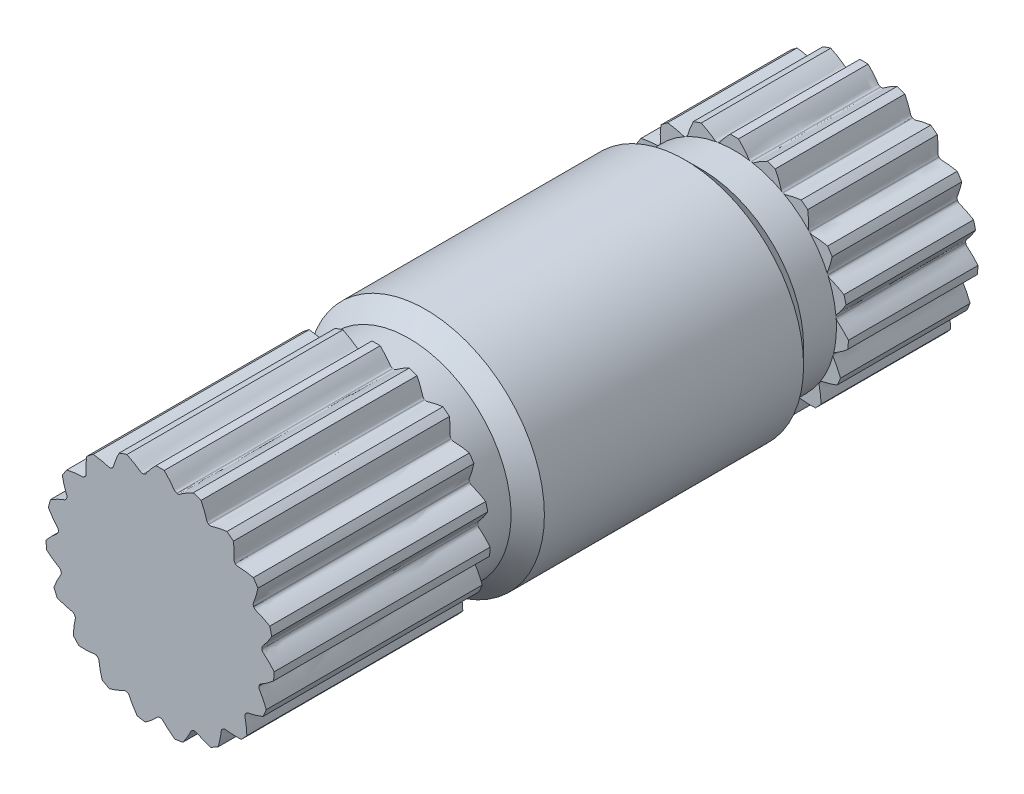
SolidWorks part; units mm, degrees
material "Alloy Steel"
ref_plane "Front Plane" through (0, 0, 0) normal (0, 0, 1) x (1, 0, 0)
ref_plane "Top Plane" through (0, 0, 0) normal (0, 1, 0) x (1, 0, 0)
ref_plane "Right Plane" through (0, 0, 0) normal (1, 0, 0) x (0, 0, -1)
sketch "Sketch12" plane through (0, 0, 0) normal (0, 0, 1) x (1, 0, 0)
  circle A0 centre (0, 0) radius 11
  dimension "D1" = 22
extrude "Boss-Extrude5" add sketch "Sketch12" along normal mid plane 30
sketch "Sketch13" plane through (0, 0, 15) normal (0, 0, 1) x (1, 0, 0)
  circle A0 centre (0, 0) radius 9.4556
  dimension "D1" = 18.9113
extrude "Boss-Extrude6" add sketch "Sketch13" along normal blind 1.587
sketch "Sketch14" plane through (0, 0, -15) normal (0, 0, -1) x (-1, 0, 0)
  circle A0 centre (0, 0) radius 9.4556
  dimension "D1" = 18.9113
extrude "Boss-Extrude7" add sketch "Sketch14" along normal blind 1.587
sketch "Sketch15" plane through (0, 0, 16.587) normal (0, 0, 1) x (1, 0, 0)
  line L0 (5.7898, -7.4758) -> (5.8078, -7.4618)
  line L1 (5.8078, -7.4618) -> (5.8257, -7.4478)
  line L2 (7.9035, -5.1908) -> (7.9159, -5.1717)
  line L3 (7.9159, -5.1717) -> (7.9284, -5.1527)
  line L4 (9.1607, -2.3432) -> (9.1663, -2.3212)
  line L5 (9.1663, -2.3212) -> (9.1719, -2.2992)
  line L6 (9.4252, 0.7582) -> (9.4233, 0.7808)
  line L7 (9.4233, 0.7808) -> (9.4214, 0.8035)
  line L8 (8.6683, 3.7775) -> (8.6592, 3.7983)
  line L9 (8.6592, 3.7983) -> (8.6501, 3.8191)
  line L10 (6.9721, 6.3874) -> (6.9567, 6.4041)
  line L11 (6.9567, 6.4041) -> (6.9413, 6.4208)
  line L12 (4.5204, 8.3051) -> (4.5004, 8.316)
  line L13 (4.5004, 8.316) -> (4.4804, 8.3268)
  line L14 (1.5788, 9.3229) -> (1.5563, 9.3267)
  line L15 (1.5563, 9.3267) -> (1.5339, 9.3304)
  line L16 (-1.5339, 9.3304) -> (-1.5563, 9.3267)
  line L17 (-1.5563, 9.3267) -> (-1.5788, 9.3229)
  line L18 (-4.4804, 8.3268) -> (-4.5004, 8.316)
  line L19 (-4.5004, 8.316) -> (-4.5204, 8.3051)
  line L20 (-6.9413, 6.4208) -> (-6.9567, 6.4041)
  line L21 (-6.9567, 6.4041) -> (-6.9721, 6.3874)
  line L22 (-8.6501, 3.8191) -> (-8.6592, 3.7983)
  line L23 (-8.6592, 3.7983) -> (-8.6683, 3.7775)
  line L24 (-9.4214, 0.8035) -> (-9.4233, 0.7808)
  line L25 (-9.4233, 0.7808) -> (-9.4252, 0.7582)
  line L26 (-9.1719, -2.2992) -> (-9.1663, -2.3212)
  line L27 (-9.1663, -2.3212) -> (-9.1607, -2.3432)
  line L28 (-7.9284, -5.1527) -> (-7.9159, -5.1717)
  line L29 (-7.9159, -5.1717) -> (-7.9035, -5.1908)
  line L30 (-5.8257, -7.4478) -> (-5.8078, -7.4618)
  line L31 (-5.8078, -7.4618) -> (-5.7898, -7.4758)
  line L32 (-3.0917, -8.9359) -> (-3.0702, -8.9433)
  line L33 (-3.0702, -8.9433) -> (-3.0487, -8.9507)
  line L34 (-0.0227, -9.4556) -> (0, -9.4556)
  line L35 (0, -9.4556) -> (0.0227, -9.4556)
  line L36 (3.0487, -8.9507) -> (3.0702, -8.9433)
  line L37 (3.0702, -8.9433) -> (3.0917, -8.9359)
  arc A0 (4.6925, -9.4774) -> (5.3676, -9.1121) centre (0, 0) ccw
  arc A1 (7.5156, -7.4402) -> (8.0355, -6.8755) centre (0, 0) ccw
  arc A2 (9.5242, -4.5968) -> (9.8326, -3.8939) centre (0, 0) ccw
  arc A3 (10.5007, -1.2552) -> (10.5641, -0.4903) centre (0, 0) ccw
  arc A4 (10.3394, 2.2224) -> (10.1509, 2.9665) centre (0, 0) ccw
  arc A5 (9.0575, 5.4591) -> (8.6377, 6.1017) centre (0, 0) ccw
  arc A6 (6.7942, 8.1043) -> (6.1885, 8.5758) centre (0, 0) ccw
  arc A7 (3.7946, 9.8713) -> (3.0686, 10.1205) centre (0, 0) ccw
  arc A8 (0.3838, 10.5685) -> (-0.3838, 10.5685) centre (0, 0) ccw
  arc A9 (-3.0686, 10.1205) -> (-3.7946, 9.8713) centre (0, 0) ccw
  arc A10 (-6.1885, 8.5758) -> (-6.7942, 8.1043) centre (0, 0) ccw
  arc A11 (-8.6377, 6.1017) -> (-9.0575, 5.4591) centre (0, 0) ccw
  arc A12 (-10.1509, 2.9665) -> (-10.3394, 2.2224) centre (0, 0) ccw
  arc A13 (-10.5641, -0.4903) -> (-10.5007, -1.2552) centre (0, 0) ccw
  arc A14 (-9.8326, -3.8939) -> (-9.5242, -4.5968) centre (0, 0) ccw
  arc A15 (-8.0355, -6.8755) -> (-7.5156, -7.4402) centre (0, 0) ccw
  arc A16 (-5.3676, -9.1121) -> (-4.6925, -9.4774) centre (0, 0) ccw
  arc A17 (-2.1181, -10.3612) -> (-1.361, -10.4876) centre (0, 0) ccw
  arc A18 (1.361, -10.4876) -> (2.1181, -10.3612) centre (0, 0) ccw
  spline S0 degree 3 poles (3.0917, -8.9359) (3.1544, -8.9142) (3.2184, -8.911) (3.3396, -8.938) (3.397, -8.9729) (3.5767, -9.0624) (3.828, -9.1783) (4.24, -9.3384) (4.5379, -9.4334) (4.6925, -9.4774) knots 0 0 0 0 0.125 0.125 0.25 0.25 0.5 0.75 1 1 1 1
  spline S1 degree 3 poles (5.3676, -9.1121) (5.4153, -8.9586) (5.4987, -8.6572) (5.5901, -8.2247) (5.6305, -7.951) (5.6538, -7.7516) (5.656, -7.6845) (5.6997, -7.5682) (5.7374, -7.5164) (5.7898, -7.4758) knots 0 0 0 0 0.25 0.5 0.75 0.75 0.875 0.875 1 1 1 1
  spline S2 degree 3 poles (5.8257, -7.4478) (5.8779, -7.407) (5.9374, -7.3832) (6.0608, -7.3694) (6.1265, -7.3837) (6.3255, -7.41) (6.6008, -7.438) (7.0425, -7.4557) (7.3551, -7.4488) (7.5156, -7.4402) knots 0 0 0 0 0.125 0.125 0.25 0.25 0.5 0.75 1 1 1 1
  spline S3 degree 3 poles (8.0355, -6.8755) (8.0308, -6.7148) (8.0117, -6.4027) (7.9577, -5.964) (7.9071, -5.692) (7.8645, -5.4958) (7.8447, -5.4316) (7.8483, -5.3075) (7.8671, -5.2462) (7.9035, -5.1908) knots 0 0 0 0 0.25 0.5 0.75 0.75 0.875 0.875 1 1 1 1
  spline S4 degree 3 poles (7.9284, -5.1527) (7.9645, -5.0971) (8.013, -5.0552) (8.1253, -5.0021) (8.192, -4.9944) (8.3888, -4.9546) (8.6583, -4.8918) (9.0817, -4.765) (9.3752, -4.6571) (9.5242, -4.5968) knots 0 0 0 0 0.125 0.125 0.25 0.25 0.5 0.75 1 1 1 1
  spline S5 degree 3 poles (9.8326, -3.8939) (9.7759, -3.7434) (9.6566, -3.4544) (9.4631, -3.057) (9.3268, -2.8161) (9.2228, -2.6445) (9.1833, -2.5901) (9.1463, -2.4716) (9.1443, -2.4075) (9.1607, -2.3432) knots 0 0 0 0 0.25 0.5 0.75 0.75 0.875 0.875 1 1 1 1
  spline S6 degree 3 poles (9.1719, -2.2992) (9.188, -2.2349) (9.2203, -2.1795) (9.3092, -2.0928) (9.3699, -2.0638) (9.543, -1.9624) (9.7775, -1.8154) (10.1368, -1.558) (10.3793, -1.3606) (10.5007, -1.2552) knots 0 0 0 0 0.125 0.125 0.25 0.25 0.5 0.75 1 1 1 1
  spline S7 degree 3 poles (10.5641, -0.4903) (10.4617, -0.3663) (10.255, -0.1317) (9.9429, 0.1813) (9.7359, 0.3649) (9.5818, 0.4935) (9.5267, 0.532) (9.4533, 0.6322) (9.4305, 0.6921) (9.4252, 0.7582) knots 0 0 0 0 0.25 0.5 0.75 0.75 0.875 0.875 1 1 1 1
  spline S8 degree 3 poles (9.4214, 0.8035) (9.4158, 0.8695) (9.4284, 0.9324) (9.4844, 1.0433) (9.5323, 1.0904) (9.6631, 1.2426) (9.8372, 1.4577) (10.0935, 1.8179) (10.2588, 2.0833) (10.3394, 2.2224) knots 0 0 0 0 0.125 0.125 0.25 0.25 0.5 0.75 1 1 1 1
  spline S9 degree 3 poles (10.1509, 2.9665) (10.0138, 3.0504) (9.7422, 3.2052) (9.3453, 3.4) (9.0899, 3.5063) (8.9024, 3.5779) (8.8378, 3.5965) (8.7358, 3.6674) (8.6948, 3.7167) (8.6683, 3.7775) knots 0 0 0 0 0.25 0.5 0.75 0.75 0.875 0.875 1 1 1 1
  spline S10 degree 3 poles (8.6501, 3.8191) (8.6233, 3.8797) (8.6148, 3.9433) (8.6317, 4.0663) (8.6618, 4.1264) (8.7361, 4.3129) (8.8308, 4.5729) (8.9563, 4.9967) (9.0265, 5.3014) (9.0575, 5.4591) knots 0 0 0 0 0.125 0.125 0.25 0.25 0.5 0.75 1 1 1 1
  spline S11 degree 3 poles (8.6377, 6.1017) (8.4808, 6.1366) (8.1736, 6.1948) (7.735, 6.2502) (7.4588, 6.2678) (7.2583, 6.2747) (7.1911, 6.2713) (7.0717, 6.3052) (7.0169, 6.3385) (6.9721, 6.3874) knots 0 0 0 0 0.25 0.5 0.75 0.75 0.875 0.875 1 1 1 1
  spline S12 degree 3 poles (6.9413, 6.4208) (6.8963, 6.4695) (6.8676, 6.5268) (6.8437, 6.6487) (6.8526, 6.7153) (6.8624, 6.9158) (6.8676, 7.1925) (6.8486, 7.6341) (6.816, 7.9451) (6.7942, 8.1043) knots 0 0 0 0 0.125 0.125 0.25 0.25 0.5 0.75 1 1 1 1
  spline S13 degree 3 poles (6.1885, 8.5758) (6.0287, 8.5578) (5.7193, 8.5131) (5.2865, 8.4231) (5.0196, 8.3501) (4.8276, 8.2914) (4.7652, 8.2664) (4.6412, 8.2597) (4.5786, 8.2734) (4.5204, 8.3051) knots 0 0 0 0 0.25 0.5 0.75 0.75 0.875 0.875 1 1 1 1
  spline S14 degree 3 poles (4.4804, 8.3268) (4.422, 8.3582) (4.3763, 8.4031) (4.3141, 8.5106) (4.3009, 8.5765) (4.245, 8.7693) (4.1601, 9.0326) (3.9988, 9.4442) (3.8669, 9.7277) (3.7946, 9.8713) knots 0 0 0 0 0.125 0.125 0.25 0.25 0.5 0.75 1 1 1 1
  spline S15 degree 3 poles (3.0686, 10.1205) (2.9233, 10.0517) (2.6452, 9.9089) (2.2651, 9.6832) (2.0363, 9.5275) (1.8738, 9.4097) (1.8229, 9.3658) (1.7078, 9.3192) (1.6441, 9.3118) (1.5788, 9.3229) knots 0 0 0 0 0.25 0.5 0.75 0.75 0.875 0.875 1 1 1 1
  spline S16 degree 3 poles (1.5339, 9.3304) (1.4685, 9.3411) (1.4107, 9.3688) (1.3169, 9.4502) (1.283, 9.5083) (1.1676, 9.6725) (1.0018, 9.894) (0.7156, 10.2309) (0.4988, 10.4563) (0.3838, 10.5685) knots 0 0 0 0 0.125 0.125 0.25 0.25 0.5 0.75 1 1 1 1
  spline S17 degree 3 poles (-0.3838, 10.5685) (-0.4988, 10.4563) (-0.7156, 10.2309) (-1.0018, 9.894) (-1.1676, 9.6725) (-1.283, 9.5083) (-1.3169, 9.4502) (-1.4107, 9.3688) (-1.4685, 9.3411) (-1.5339, 9.3304) knots 0 0 0 0 0.25 0.5 0.75 0.75 0.875 0.875 1 1 1 1
  spline S18 degree 3 poles (-1.5788, 9.3229) (-1.6441, 9.3118) (-1.7078, 9.3192) (-1.8229, 9.3658) (-1.8738, 9.4097) (-2.0363, 9.5275) (-2.2651, 9.6832) (-2.6452, 9.9089) (-2.9233, 10.0517) (-3.0686, 10.1205) knots 0 0 0 0 0.125 0.125 0.25 0.25 0.5 0.75 1 1 1 1
  spline S19 degree 3 poles (-3.7946, 9.8713) (-3.8669, 9.7277) (-3.9988, 9.4442) (-4.1601, 9.0326) (-4.245, 8.7693) (-4.3009, 8.5765) (-4.3141, 8.5106) (-4.3763, 8.4031) (-4.422, 8.3582) (-4.4804, 8.3268) knots 0 0 0 0 0.25 0.5 0.75 0.75 0.875 0.875 1 1 1 1
  spline S20 degree 3 poles (-4.5204, 8.3051) (-4.5786, 8.2734) (-4.6412, 8.2597) (-4.7652, 8.2664) (-4.8276, 8.2914) (-5.0196, 8.3501) (-5.2865, 8.4231) (-5.7193, 8.5131) (-6.0287, 8.5578) (-6.1885, 8.5758) knots 0 0 0 0 0.125 0.125 0.25 0.25 0.5 0.75 1 1 1 1
  spline S21 degree 3 poles (-6.7942, 8.1043) (-6.816, 7.9451) (-6.8486, 7.6341) (-6.8676, 7.1925) (-6.8624, 6.9158) (-6.8526, 6.7153) (-6.8437, 6.6487) (-6.8676, 6.5268) (-6.8963, 6.4695) (-6.9413, 6.4208) knots 0 0 0 0 0.25 0.5 0.75 0.75 0.875 0.875 1 1 1 1
  spline S22 degree 3 poles (-6.9721, 6.3874) (-7.0169, 6.3385) (-7.0717, 6.3052) (-7.1911, 6.2713) (-7.2583, 6.2747) (-7.4588, 6.2678) (-7.735, 6.2502) (-8.1736, 6.1948) (-8.4808, 6.1366) (-8.6377, 6.1017) knots 0 0 0 0 0.125 0.125 0.25 0.25 0.5 0.75 1 1 1 1
  spline S23 degree 3 poles (-9.0575, 5.4591) (-9.0265, 5.3014) (-8.9563, 4.9967) (-8.8308, 4.5729) (-8.7361, 4.3129) (-8.6618, 4.1264) (-8.6317, 4.0663) (-8.6148, 3.9433) (-8.6233, 3.8797) (-8.6501, 3.8191) knots 0 0 0 0 0.25 0.5 0.75 0.75 0.875 0.875 1 1 1 1
  spline S24 degree 3 poles (-8.6683, 3.7775) (-8.6948, 3.7167) (-8.7358, 3.6674) (-8.8378, 3.5965) (-8.9024, 3.5779) (-9.0899, 3.5063) (-9.3453, 3.4) (-9.7422, 3.2052) (-10.0138, 3.0504) (-10.1509, 2.9665) knots 0 0 0 0 0.125 0.125 0.25 0.25 0.5 0.75 1 1 1 1
  spline S25 degree 3 poles (-10.3394, 2.2224) (-10.2588, 2.0833) (-10.0935, 1.8179) (-9.8372, 1.4577) (-9.6631, 1.2426) (-9.5323, 1.0904) (-9.4844, 1.0433) (-9.4284, 0.9324) (-9.4158, 0.8695) (-9.4214, 0.8035) knots 0 0 0 0 0.25 0.5 0.75 0.75 0.875 0.875 1 1 1 1
  spline S26 degree 3 poles (-9.4252, 0.7582) (-9.4305, 0.6921) (-9.4533, 0.6322) (-9.5267, 0.532) (-9.5818, 0.4935) (-9.7359, 0.3649) (-9.9429, 0.1813) (-10.255, -0.1317) (-10.4617, -0.3663) (-10.5641, -0.4903) knots 0 0 0 0 0.125 0.125 0.25 0.25 0.5 0.75 1 1 1 1
  spline S27 degree 3 poles (-10.5007, -1.2552) (-10.3793, -1.3606) (-10.1368, -1.558) (-9.7775, -1.8154) (-9.543, -1.9624) (-9.3699, -2.0638) (-9.3092, -2.0928) (-9.2203, -2.1795) (-9.188, -2.2349) (-9.1719, -2.2992) knots 0 0 0 0 0.25 0.5 0.75 0.75 0.875 0.875 1 1 1 1
  spline S28 degree 3 poles (-9.1607, -2.3432) (-9.1443, -2.4075) (-9.1463, -2.4716) (-9.1833, -2.5901) (-9.2228, -2.6445) (-9.3268, -2.8161) (-9.4631, -3.057) (-9.6566, -3.4544) (-9.7759, -3.7434) (-9.8326, -3.8939) knots 0 0 0 0 0.125 0.125 0.25 0.25 0.5 0.75 1 1 1 1
  spline S29 degree 3 poles (-9.5242, -4.5968) (-9.3752, -4.6571) (-9.0817, -4.765) (-8.6583, -4.8918) (-8.3888, -4.9546) (-8.192, -4.9944) (-8.1253, -5.0021) (-8.013, -5.0552) (-7.9645, -5.0971) (-7.9284, -5.1527) knots 0 0 0 0 0.25 0.5 0.75 0.75 0.875 0.875 1 1 1 1
  spline S30 degree 3 poles (-7.9035, -5.1908) (-7.8671, -5.2462) (-7.8483, -5.3075) (-7.8447, -5.4316) (-7.8645, -5.4958) (-7.9071, -5.692) (-7.9577, -5.964) (-8.0117, -6.4027) (-8.0308, -6.7148) (-8.0355, -6.8755) knots 0 0 0 0 0.125 0.125 0.25 0.25 0.5 0.75 1 1 1 1
  spline S31 degree 3 poles (-7.5156, -7.4402) (-7.3551, -7.4488) (-7.0425, -7.4557) (-6.6008, -7.438) (-6.3255, -7.41) (-6.1265, -7.3837) (-6.0608, -7.3694) (-5.9374, -7.3832) (-5.8779, -7.407) (-5.8257, -7.4478) knots 0 0 0 0 0.25 0.5 0.75 0.75 0.875 0.875 1 1 1 1
  spline S32 degree 3 poles (-5.7898, -7.4758) (-5.7374, -7.5164) (-5.6997, -7.5682) (-5.656, -7.6845) (-5.6538, -7.7516) (-5.6305, -7.951) (-5.5901, -8.2247) (-5.4987, -8.6572) (-5.4153, -8.9586) (-5.3676, -9.1121) knots 0 0 0 0 0.125 0.125 0.25 0.25 0.5 0.75 1 1 1 1
  spline S33 degree 3 poles (-4.6925, -9.4774) (-4.5379, -9.4334) (-4.24, -9.3384) (-3.828, -9.1783) (-3.5767, -9.0624) (-3.397, -8.9729) (-3.3396, -8.938) (-3.2184, -8.911) (-3.1544, -8.9142) (-3.0917, -8.9359) knots 0 0 0 0 0.25 0.5 0.75 0.75 0.875 0.875 1 1 1 1
  spline S34 degree 3 poles (-3.0487, -8.9507) (-2.986, -8.972) (-2.9335, -9.0088) (-2.8544, -9.1046) (-2.8306, -9.1674) (-2.7437, -9.3484) (-2.6166, -9.5942) (-2.3898, -9.9736) (-2.2131, -10.2315) (-2.1181, -10.3612) knots 0 0 0 0 0.125 0.125 0.25 0.25 0.5 0.75 1 1 1 1
  spline S35 degree 3 poles (-1.361, -10.4876) (-1.229, -10.3957) (-0.9781, -10.2091) (-0.6404, -9.9239) (-0.4404, -9.7327) (-0.2995, -9.5898) (-0.2565, -9.5381) (-0.1506, -9.4732) (-0.089, -9.4555) (-0.0227, -9.4556) knots 0 0 0 0 0.25 0.5 0.75 0.75 0.875 0.875 1 1 1 1
  spline S36 degree 3 poles (0.0227, -9.4556) (0.089, -9.4555) (0.1506, -9.4732) (0.2565, -9.5381) (0.2995, -9.5898) (0.4404, -9.7327) (0.6404, -9.9239) (0.9781, -10.2091) (1.229, -10.3957) (1.361, -10.4876) knots 0 0 0 0 0.125 0.125 0.25 0.25 0.5 0.75 1 1 1 1
  spline S37 degree 3 poles (2.1181, -10.3612) (2.2131, -10.2315) (2.3898, -9.9736) (2.6166, -9.5942) (2.7437, -9.3484) (2.8306, -9.1674) (2.8544, -9.1046) (2.9335, -9.0088) (2.986, -8.972) (3.0487, -8.9507) knots 0 0 0 0 0.25 0.5 0.75 0.75 0.875 0.875 1 1 1 1
extrude "Boss-Extrude8" add sketch "Sketch15" along normal blind 20
sketch "Sketch17" plane through (0, 0, -16.587) normal (0, 0, -1) x (-1, 0, 0)
  line L0 (5.7898, -7.4758) -> (5.8078, -7.4618)
  line L1 (5.8078, -7.4618) -> (5.8257, -7.4478)
  line L2 (7.9035, -5.1908) -> (7.9159, -5.1717)
  line L3 (7.9159, -5.1717) -> (7.9284, -5.1527)
  line L4 (9.1607, -2.3432) -> (9.1663, -2.3212)
  line L5 (9.1663, -2.3212) -> (9.1719, -2.2992)
  line L6 (9.4252, 0.7582) -> (9.4233, 0.7808)
  line L7 (9.4233, 0.7808) -> (9.4214, 0.8035)
  line L8 (8.6683, 3.7775) -> (8.6592, 3.7983)
  line L9 (8.6592, 3.7983) -> (8.6501, 3.8191)
  line L10 (6.9721, 6.3874) -> (6.9567, 6.4041)
  line L11 (6.9567, 6.4041) -> (6.9413, 6.4208)
  line L12 (4.5204, 8.3051) -> (4.5004, 8.316)
  line L13 (4.5004, 8.316) -> (4.4804, 8.3268)
  line L14 (1.5788, 9.3229) -> (1.5563, 9.3267)
  line L15 (1.5563, 9.3267) -> (1.5339, 9.3304)
  line L16 (-1.5339, 9.3304) -> (-1.5563, 9.3267)
  line L17 (-1.5563, 9.3267) -> (-1.5788, 9.3229)
  line L18 (-4.4804, 8.3268) -> (-4.5004, 8.316)
  line L19 (-4.5004, 8.316) -> (-4.5204, 8.3051)
  line L20 (-6.9413, 6.4208) -> (-6.9567, 6.4041)
  line L21 (-6.9567, 6.4041) -> (-6.9721, 6.3874)
  line L22 (-8.6501, 3.8191) -> (-8.6592, 3.7983)
  line L23 (-8.6592, 3.7983) -> (-8.6683, 3.7775)
  line L24 (-9.4214, 0.8035) -> (-9.4233, 0.7808)
  line L25 (-9.4233, 0.7808) -> (-9.4252, 0.7582)
  line L26 (-9.1719, -2.2992) -> (-9.1663, -2.3212)
  line L27 (-9.1663, -2.3212) -> (-9.1607, -2.3432)
  line L28 (-7.9284, -5.1527) -> (-7.9159, -5.1717)
  line L29 (-7.9159, -5.1717) -> (-7.9035, -5.1908)
  line L30 (-5.8257, -7.4478) -> (-5.8078, -7.4618)
  line L31 (-5.8078, -7.4618) -> (-5.7898, -7.4758)
  line L32 (-3.0917, -8.9359) -> (-3.0702, -8.9433)
  line L33 (-3.0702, -8.9433) -> (-3.0487, -8.9507)
  line L34 (-0.0227, -9.4556) -> (0, -9.4556)
  line L35 (0, -9.4556) -> (0.0227, -9.4556)
  line L36 (3.0487, -8.9507) -> (3.0702, -8.9433)
  line L37 (3.0702, -8.9433) -> (3.0917, -8.9359)
  arc A0 (4.6925, -9.4774) -> (5.3676, -9.1121) centre (0, 0) ccw
  arc A1 (7.5156, -7.4402) -> (8.0355, -6.8755) centre (0, 0) ccw
  arc A2 (9.5242, -4.5968) -> (9.8326, -3.8939) centre (0, 0) ccw
  arc A3 (10.5007, -1.2552) -> (10.5641, -0.4903) centre (0, 0) ccw
  arc A4 (10.3394, 2.2224) -> (10.1509, 2.9665) centre (0, 0) ccw
  arc A5 (9.0575, 5.4591) -> (8.6377, 6.1017) centre (0, 0) ccw
  arc A6 (6.7942, 8.1043) -> (6.1885, 8.5758) centre (0, 0) ccw
  arc A7 (3.7946, 9.8713) -> (3.0686, 10.1205) centre (0, 0) ccw
  arc A8 (0.3838, 10.5685) -> (-0.3838, 10.5685) centre (0, 0) ccw
  arc A9 (-3.0686, 10.1205) -> (-3.7946, 9.8713) centre (0, 0) ccw
  arc A10 (-6.1885, 8.5758) -> (-6.7942, 8.1043) centre (0, 0) ccw
  arc A11 (-8.6377, 6.1017) -> (-9.0575, 5.4591) centre (0, 0) ccw
  arc A12 (-10.1509, 2.9665) -> (-10.3394, 2.2224) centre (0, 0) ccw
  arc A13 (-10.5641, -0.4903) -> (-10.5007, -1.2552) centre (0, 0) ccw
  arc A14 (-9.8326, -3.8939) -> (-9.5242, -4.5968) centre (0, 0) ccw
  arc A15 (-8.0355, -6.8755) -> (-7.5156, -7.4402) centre (0, 0) ccw
  arc A16 (-5.3676, -9.1121) -> (-4.6925, -9.4774) centre (0, 0) ccw
  arc A17 (-2.1181, -10.3612) -> (-1.361, -10.4876) centre (0, 0) ccw
  arc A18 (1.361, -10.4876) -> (2.1181, -10.3612) centre (0, 0) ccw
  spline S0 degree 3 poles (3.0917, -8.9359) (3.1544, -8.9142) (3.2184, -8.911) (3.3396, -8.938) (3.397, -8.9729) (3.5767, -9.0624) (3.828, -9.1783) (4.24, -9.3384) (4.5379, -9.4334) (4.6925, -9.4774) knots 0 0 0 0 0.125 0.125 0.25 0.25 0.5 0.75 1 1 1 1
  spline S1 degree 3 poles (5.3676, -9.1121) (5.4153, -8.9586) (5.4987, -8.6572) (5.5901, -8.2247) (5.6305, -7.951) (5.6538, -7.7516) (5.656, -7.6845) (5.6997, -7.5682) (5.7374, -7.5164) (5.7898, -7.4758) knots 0 0 0 0 0.25 0.5 0.75 0.75 0.875 0.875 1 1 1 1
  spline S2 degree 3 poles (5.8257, -7.4478) (5.8779, -7.407) (5.9374, -7.3832) (6.0608, -7.3694) (6.1265, -7.3837) (6.3255, -7.41) (6.6008, -7.438) (7.0425, -7.4557) (7.3551, -7.4488) (7.5156, -7.4402) knots 0 0 0 0 0.125 0.125 0.25 0.25 0.5 0.75 1 1 1 1
  spline S3 degree 3 poles (8.0355, -6.8755) (8.0308, -6.7148) (8.0117, -6.4027) (7.9577, -5.964) (7.9071, -5.692) (7.8645, -5.4958) (7.8447, -5.4316) (7.8483, -5.3075) (7.8671, -5.2462) (7.9035, -5.1908) knots 0 0 0 0 0.25 0.5 0.75 0.75 0.875 0.875 1 1 1 1
  spline S4 degree 3 poles (7.9284, -5.1527) (7.9645, -5.0971) (8.013, -5.0552) (8.1253, -5.0021) (8.192, -4.9944) (8.3888, -4.9546) (8.6583, -4.8918) (9.0817, -4.765) (9.3752, -4.6571) (9.5242, -4.5968) knots 0 0 0 0 0.125 0.125 0.25 0.25 0.5 0.75 1 1 1 1
  spline S5 degree 3 poles (9.8326, -3.8939) (9.7759, -3.7434) (9.6566, -3.4544) (9.4631, -3.057) (9.3268, -2.8161) (9.2228, -2.6445) (9.1833, -2.5901) (9.1463, -2.4716) (9.1443, -2.4075) (9.1607, -2.3432) knots 0 0 0 0 0.25 0.5 0.75 0.75 0.875 0.875 1 1 1 1
  spline S6 degree 3 poles (9.1719, -2.2992) (9.188, -2.2349) (9.2203, -2.1795) (9.3092, -2.0928) (9.3699, -2.0638) (9.543, -1.9624) (9.7775, -1.8154) (10.1368, -1.558) (10.3793, -1.3606) (10.5007, -1.2552) knots 0 0 0 0 0.125 0.125 0.25 0.25 0.5 0.75 1 1 1 1
  spline S7 degree 3 poles (10.5641, -0.4903) (10.4617, -0.3663) (10.255, -0.1317) (9.9429, 0.1813) (9.7359, 0.3649) (9.5818, 0.4935) (9.5267, 0.532) (9.4533, 0.6322) (9.4305, 0.6921) (9.4252, 0.7582) knots 0 0 0 0 0.25 0.5 0.75 0.75 0.875 0.875 1 1 1 1
  spline S8 degree 3 poles (9.4214, 0.8035) (9.4158, 0.8695) (9.4284, 0.9324) (9.4844, 1.0433) (9.5323, 1.0904) (9.6631, 1.2426) (9.8372, 1.4577) (10.0935, 1.8179) (10.2588, 2.0833) (10.3394, 2.2224) knots 0 0 0 0 0.125 0.125 0.25 0.25 0.5 0.75 1 1 1 1
  spline S9 degree 3 poles (10.1509, 2.9665) (10.0138, 3.0504) (9.7422, 3.2052) (9.3453, 3.4) (9.0899, 3.5063) (8.9024, 3.5779) (8.8378, 3.5965) (8.7358, 3.6674) (8.6948, 3.7167) (8.6683, 3.7775) knots 0 0 0 0 0.25 0.5 0.75 0.75 0.875 0.875 1 1 1 1
  spline S10 degree 3 poles (8.6501, 3.8191) (8.6233, 3.8797) (8.6148, 3.9433) (8.6317, 4.0663) (8.6618, 4.1264) (8.7361, 4.3129) (8.8308, 4.5729) (8.9563, 4.9967) (9.0265, 5.3014) (9.0575, 5.4591) knots 0 0 0 0 0.125 0.125 0.25 0.25 0.5 0.75 1 1 1 1
  spline S11 degree 3 poles (8.6377, 6.1017) (8.4808, 6.1366) (8.1736, 6.1948) (7.735, 6.2502) (7.4588, 6.2678) (7.2583, 6.2747) (7.1911, 6.2713) (7.0717, 6.3052) (7.0169, 6.3385) (6.9721, 6.3874) knots 0 0 0 0 0.25 0.5 0.75 0.75 0.875 0.875 1 1 1 1
  spline S12 degree 3 poles (6.9413, 6.4208) (6.8963, 6.4695) (6.8676, 6.5268) (6.8437, 6.6487) (6.8526, 6.7153) (6.8624, 6.9158) (6.8676, 7.1925) (6.8486, 7.6341) (6.816, 7.9451) (6.7942, 8.1043) knots 0 0 0 0 0.125 0.125 0.25 0.25 0.5 0.75 1 1 1 1
  spline S13 degree 3 poles (6.1885, 8.5758) (6.0287, 8.5578) (5.7193, 8.5131) (5.2865, 8.4231) (5.0196, 8.3501) (4.8276, 8.2914) (4.7652, 8.2664) (4.6412, 8.2597) (4.5786, 8.2734) (4.5204, 8.3051) knots 0 0 0 0 0.25 0.5 0.75 0.75 0.875 0.875 1 1 1 1
  spline S14 degree 3 poles (4.4804, 8.3268) (4.422, 8.3582) (4.3763, 8.4031) (4.3141, 8.5106) (4.3009, 8.5765) (4.245, 8.7693) (4.1601, 9.0326) (3.9988, 9.4442) (3.8669, 9.7277) (3.7946, 9.8713) knots 0 0 0 0 0.125 0.125 0.25 0.25 0.5 0.75 1 1 1 1
  spline S15 degree 3 poles (3.0686, 10.1205) (2.9233, 10.0517) (2.6452, 9.9089) (2.2651, 9.6832) (2.0363, 9.5275) (1.8738, 9.4097) (1.8229, 9.3658) (1.7078, 9.3192) (1.6441, 9.3118) (1.5788, 9.3229) knots 0 0 0 0 0.25 0.5 0.75 0.75 0.875 0.875 1 1 1 1
  spline S16 degree 3 poles (1.5339, 9.3304) (1.4685, 9.3411) (1.4107, 9.3688) (1.3169, 9.4502) (1.283, 9.5083) (1.1676, 9.6725) (1.0018, 9.894) (0.7156, 10.2309) (0.4988, 10.4563) (0.3838, 10.5685) knots 0 0 0 0 0.125 0.125 0.25 0.25 0.5 0.75 1 1 1 1
  spline S17 degree 3 poles (-0.3838, 10.5685) (-0.4988, 10.4563) (-0.7156, 10.2309) (-1.0018, 9.894) (-1.1676, 9.6725) (-1.283, 9.5083) (-1.3169, 9.4502) (-1.4107, 9.3688) (-1.4685, 9.3411) (-1.5339, 9.3304) knots 0 0 0 0 0.25 0.5 0.75 0.75 0.875 0.875 1 1 1 1
  spline S18 degree 3 poles (-1.5788, 9.3229) (-1.6441, 9.3118) (-1.7078, 9.3192) (-1.8229, 9.3658) (-1.8738, 9.4097) (-2.0363, 9.5275) (-2.2651, 9.6832) (-2.6452, 9.9089) (-2.9233, 10.0517) (-3.0686, 10.1205) knots 0 0 0 0 0.125 0.125 0.25 0.25 0.5 0.75 1 1 1 1
  spline S19 degree 3 poles (-3.7946, 9.8713) (-3.8669, 9.7277) (-3.9988, 9.4442) (-4.1601, 9.0326) (-4.245, 8.7693) (-4.3009, 8.5765) (-4.3141, 8.5106) (-4.3763, 8.4031) (-4.422, 8.3582) (-4.4804, 8.3268) knots 0 0 0 0 0.25 0.5 0.75 0.75 0.875 0.875 1 1 1 1
  spline S20 degree 3 poles (-4.5204, 8.3051) (-4.5786, 8.2734) (-4.6412, 8.2597) (-4.7652, 8.2664) (-4.8276, 8.2914) (-5.0196, 8.3501) (-5.2865, 8.4231) (-5.7193, 8.5131) (-6.0287, 8.5578) (-6.1885, 8.5758) knots 0 0 0 0 0.125 0.125 0.25 0.25 0.5 0.75 1 1 1 1
  spline S21 degree 3 poles (-6.7942, 8.1043) (-6.816, 7.9451) (-6.8486, 7.6341) (-6.8676, 7.1925) (-6.8624, 6.9158) (-6.8526, 6.7153) (-6.8437, 6.6487) (-6.8676, 6.5268) (-6.8963, 6.4695) (-6.9413, 6.4208) knots 0 0 0 0 0.25 0.5 0.75 0.75 0.875 0.875 1 1 1 1
  spline S22 degree 3 poles (-6.9721, 6.3874) (-7.0169, 6.3385) (-7.0717, 6.3052) (-7.1911, 6.2713) (-7.2583, 6.2747) (-7.4588, 6.2678) (-7.735, 6.2502) (-8.1736, 6.1948) (-8.4808, 6.1366) (-8.6377, 6.1017) knots 0 0 0 0 0.125 0.125 0.25 0.25 0.5 0.75 1 1 1 1
  spline S23 degree 3 poles (-9.0575, 5.4591) (-9.0265, 5.3014) (-8.9563, 4.9967) (-8.8308, 4.5729) (-8.7361, 4.3129) (-8.6618, 4.1264) (-8.6317, 4.0663) (-8.6148, 3.9433) (-8.6233, 3.8797) (-8.6501, 3.8191) knots 0 0 0 0 0.25 0.5 0.75 0.75 0.875 0.875 1 1 1 1
  spline S24 degree 3 poles (-8.6683, 3.7775) (-8.6948, 3.7167) (-8.7358, 3.6674) (-8.8378, 3.5965) (-8.9024, 3.5779) (-9.0899, 3.5063) (-9.3453, 3.4) (-9.7422, 3.2052) (-10.0138, 3.0504) (-10.1509, 2.9665) knots 0 0 0 0 0.125 0.125 0.25 0.25 0.5 0.75 1 1 1 1
  spline S25 degree 3 poles (-10.3394, 2.2224) (-10.2588, 2.0833) (-10.0935, 1.8179) (-9.8372, 1.4577) (-9.6631, 1.2426) (-9.5323, 1.0904) (-9.4844, 1.0433) (-9.4284, 0.9324) (-9.4158, 0.8695) (-9.4214, 0.8035) knots 0 0 0 0 0.25 0.5 0.75 0.75 0.875 0.875 1 1 1 1
  spline S26 degree 3 poles (-9.4252, 0.7582) (-9.4305, 0.6921) (-9.4533, 0.6322) (-9.5267, 0.532) (-9.5818, 0.4935) (-9.7359, 0.3649) (-9.9429, 0.1813) (-10.255, -0.1317) (-10.4617, -0.3663) (-10.5641, -0.4903) knots 0 0 0 0 0.125 0.125 0.25 0.25 0.5 0.75 1 1 1 1
  spline S27 degree 3 poles (-10.5007, -1.2552) (-10.3793, -1.3606) (-10.1368, -1.558) (-9.7775, -1.8154) (-9.543, -1.9624) (-9.3699, -2.0638) (-9.3092, -2.0928) (-9.2203, -2.1795) (-9.188, -2.2349) (-9.1719, -2.2992) knots 0 0 0 0 0.25 0.5 0.75 0.75 0.875 0.875 1 1 1 1
  spline S28 degree 3 poles (-9.1607, -2.3432) (-9.1443, -2.4075) (-9.1463, -2.4716) (-9.1833, -2.5901) (-9.2228, -2.6445) (-9.3268, -2.8161) (-9.4631, -3.057) (-9.6566, -3.4544) (-9.7759, -3.7434) (-9.8326, -3.8939) knots 0 0 0 0 0.125 0.125 0.25 0.25 0.5 0.75 1 1 1 1
  spline S29 degree 3 poles (-9.5242, -4.5968) (-9.3752, -4.6571) (-9.0817, -4.765) (-8.6583, -4.8918) (-8.3888, -4.9546) (-8.192, -4.9944) (-8.1253, -5.0021) (-8.013, -5.0552) (-7.9645, -5.0971) (-7.9284, -5.1527) knots 0 0 0 0 0.25 0.5 0.75 0.75 0.875 0.875 1 1 1 1
  spline S30 degree 3 poles (-7.9035, -5.1908) (-7.8671, -5.2462) (-7.8483, -5.3075) (-7.8447, -5.4316) (-7.8645, -5.4958) (-7.9071, -5.692) (-7.9577, -5.964) (-8.0117, -6.4027) (-8.0308, -6.7148) (-8.0355, -6.8755) knots 0 0 0 0 0.125 0.125 0.25 0.25 0.5 0.75 1 1 1 1
  spline S31 degree 3 poles (-7.5156, -7.4402) (-7.3551, -7.4488) (-7.0425, -7.4557) (-6.6008, -7.438) (-6.3255, -7.41) (-6.1265, -7.3837) (-6.0608, -7.3694) (-5.9374, -7.3832) (-5.8779, -7.407) (-5.8257, -7.4478) knots 0 0 0 0 0.25 0.5 0.75 0.75 0.875 0.875 1 1 1 1
  spline S32 degree 3 poles (-5.7898, -7.4758) (-5.7374, -7.5164) (-5.6997, -7.5682) (-5.656, -7.6845) (-5.6538, -7.7516) (-5.6305, -7.951) (-5.5901, -8.2247) (-5.4987, -8.6572) (-5.4153, -8.9586) (-5.3676, -9.1121) knots 0 0 0 0 0.125 0.125 0.25 0.25 0.5 0.75 1 1 1 1
  spline S33 degree 3 poles (-4.6925, -9.4774) (-4.5379, -9.4334) (-4.24, -9.3384) (-3.828, -9.1783) (-3.5767, -9.0624) (-3.397, -8.9729) (-3.3396, -8.938) (-3.2184, -8.911) (-3.1544, -8.9142) (-3.0917, -8.9359) knots 0 0 0 0 0.25 0.5 0.75 0.75 0.875 0.875 1 1 1 1
  spline S34 degree 3 poles (-3.0487, -8.9507) (-2.986, -8.972) (-2.9335, -9.0088) (-2.8544, -9.1046) (-2.8306, -9.1674) (-2.7437, -9.3484) (-2.6166, -9.5942) (-2.3898, -9.9736) (-2.2131, -10.2315) (-2.1181, -10.3612) knots 0 0 0 0 0.125 0.125 0.25 0.25 0.5 0.75 1 1 1 1
  spline S35 degree 3 poles (-1.361, -10.4876) (-1.229, -10.3957) (-0.9781, -10.2091) (-0.6404, -9.9239) (-0.4404, -9.7327) (-0.2995, -9.5898) (-0.2565, -9.5381) (-0.1506, -9.4732) (-0.089, -9.4555) (-0.0227, -9.4556) knots 0 0 0 0 0.25 0.5 0.75 0.75 0.875 0.875 1 1 1 1
  spline S36 degree 3 poles (0.0227, -9.4556) (0.089, -9.4555) (0.1506, -9.4732) (0.2565, -9.5381) (0.2995, -9.5898) (0.4404, -9.7327) (0.6404, -9.9239) (0.9781, -10.2091) (1.229, -10.3957) (1.361, -10.4876) knots 0 0 0 0 0.125 0.125 0.25 0.25 0.5 0.75 1 1 1 1
  spline S37 degree 3 poles (2.1181, -10.3612) (2.2131, -10.2315) (2.3898, -9.9736) (2.6166, -9.5942) (2.7437, -9.3484) (2.8306, -9.1674) (2.8544, -9.1046) (2.9335, -9.0088) (2.986, -8.972) (3.0487, -8.9507) knots 0 0 0 0 0.25 0.5 0.75 0.75 0.875 0.875 1 1 1 1
extrude "Boss-Extrude9" add sketch "Sketch17" along normal blind 12
chamfer "Chamfer1" distance 3 angle 45 2 edges at (11, 0, -15) (11, 0, 15)
